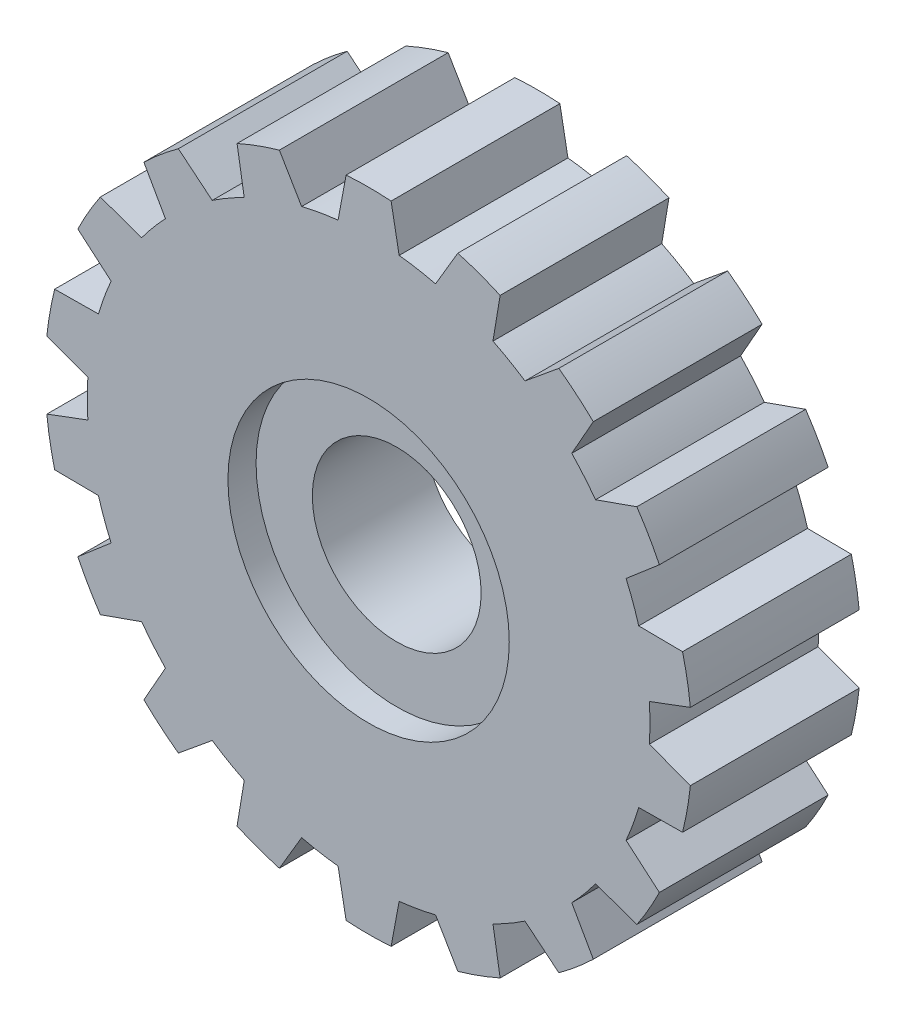
SolidWorks part; units mm, degrees
material "AISI Typ 316L Edelstahl"
ref_plane "Ebene vorne" through (0, 0, 0) normal (0, 0, 1) x (1, 0, 0)
ref_plane "Ebene oben" through (0, 0, 0) normal (0, 1, 0) x (1, 0, 0)
ref_plane "Ebene rechts" through (0, 0, 0) normal (1, 0, 0) x (0, 0, -1)
sketch "Skizze1" plane through (0, 0, 0) normal (0, 0, 1) x (1, 0, 0)
  circle A0 centre (0, 0) radius 50
  circle A2 centre (0, 0) radius 15
  dimension "D1" = 100
  dimension "D2" = 30
extrude "Aufsatz-Linear austragen1" add sketch "Skizze1" along normal blind 30
sketch "Skizze2" plane through (0, 0, 30) normal (0, 0, 1) x (1, 0, 0)
  line L3 (0, 0) -> (0, 57.5) construction
  line L4 (6, 46.6362) -> (-6, 46.6362)
  line L5 (-6, 46.6362) -> (-4, 57.3607)
  line L6 (6, 46.6362) -> (4, 57.3607)
  arc A1 (4, 57.3607) -> (-4, 57.3607) centre (0, 0) ccw
  dimension "D1" = 115
  dimension "D2" = 6
  dimension "D3" = 6
  dimension "D4" = 4
  dimension "D5" = 4
extrude "Aufsatz-Linear austragen2" add sketch "Skizze2" against normal blind 30
ref_axis "Achse1" through (0, 0, 30) along (0, 0, -1)
pattern_circular "Kreismuster1" count 18 every 20 about axis through (0, 0, 30) along (0, 0, -1) of "Aufsatz-Linear austragen2"
sketch "Skizze3" plane through (0, 0, 30) normal (0, 0, 1) x (1, 0, 0)
  circle A0 centre (0, 0) radius 25
  dimension "D1" = 50
extrude "Schnitt-Linear austragen1" cut sketch "Skizze3" against normal blind 5
sketch "Skizze4" plane through (0, 0, 0) normal (0, 0, -1) x (-1, 0, 0)
  circle A0 centre (0, 0) radius 25
  dimension "D1" = 50
extrude "Schnitt-Linear austragen2" cut sketch "Skizze4" against normal blind 5
